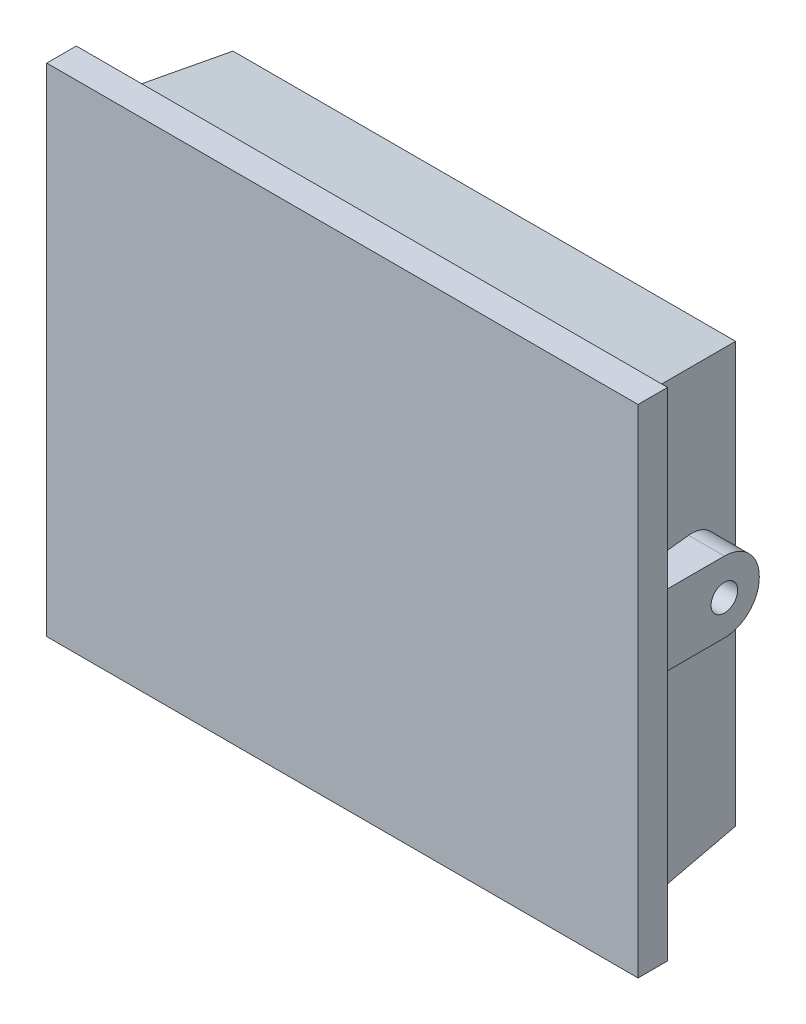
SolidWorks part; units mm, degrees
ref_plane "Alzado" through (0, 0, 0) normal (0, 0, 1) x (1, 0, 0)
ref_plane "Planta" through (0, 0, 0) normal (0, 1, 0) x (1, 0, 0)
ref_plane "Vista lateral" through (0, 0, 0) normal (1, 0, 0) x (0, 0, -1)
sketch "Croquis1" plane through (0, 0, 0) normal (0, 0, 1) x (1, 0, 0)
  line L1 (-50, -42) -> (50, -42)
  line L2 (-50, -42) -> (-50, 42)
  line L3 (-50, 42) -> (50, 42)
  line L4 (50, -42) -> (50, 42)
  line L5 (-50, -42) -> (50, 42) construction
  line L6 (-50, 42) -> (50, -42) construction
  point P0 (0, 0)
  dimension "D1" = 100
  dimension "D2" = 84
extrude "Saliente-Extruir1" add sketch "Croquis1" along normal blind 5
sketch "Croquis2" plane through (0, 0, 0) normal (0, 0, -1) x (-1, 0, 0)
  line L1 (44.5, -37.5) -> (-44.5, -37.5)
  line L2 (44.5, -37.5) -> (44.5, 37.5)
  line L3 (44.5, 37.5) -> (-44.5, 37.5)
  line L4 (-44.5, -37.5) -> (-44.5, 37.5)
  line L5 (44.5, -37.5) -> (-44.5, 37.5) construction
  line L6 (44.5, 37.5) -> (-44.5, -37.5) construction
  point P0 (0, 0)
  dimension "D1" = 89
  dimension "D2" = 75
extrude "Saliente-Extruir2" add sketch "Croquis2" along normal blind 19 draft 6
sketch "Croquis3" plane through (0, 0, 0) normal (1, 0, 0) x (0, 0, -1)
  line L0 (28.7048, 6) -> (-26.5113, 6) construction
  line L1 (0, 37.5) -> (0, -37.5) construction
  line L2 (0, 12) -> (10.1, 12)
  line L3 (0, 12) -> (0, 0)
  line L4 (0, 0) -> (10.1, 0)
  line L5 (16, 6.1) -> (16, 5.9)
  arc A0 (10.1, 0) -> (16, 5.9) centre (10.1, 5.9) ccw
  arc A1 (10.1, 12) -> (16, 6.1) centre (10.1, 6.1) cw
  circle A2 centre (10.1, 5.9) radius 2.25
  point P11 (16, 0)
  point P14 (16, 12)
  dimension "D4" = 5.9
  dimension "D6" = 4.5
  dimension "D1" = 30
  dimension "D2" = 12
  dimension "D3" = 16
  dimension "D5" = 10.1
extrude "Saliente-Extruir3" add sketch "Croquis3" along normal mid plane 99
